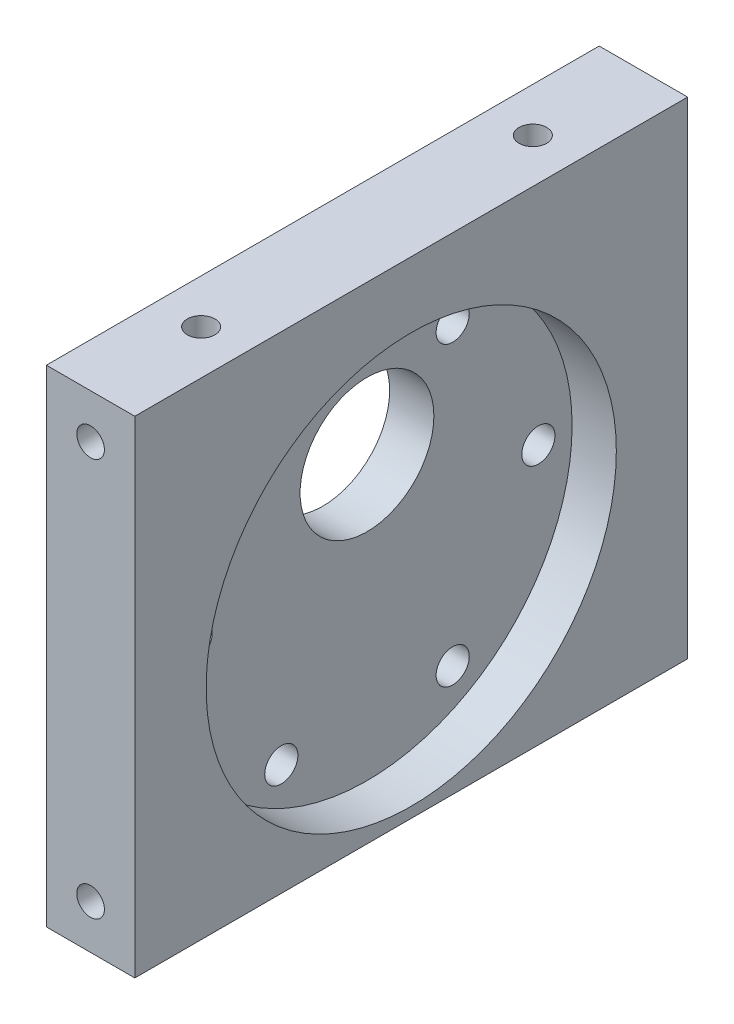
SolidWorks part; units mm, degrees
material "POM Acetal Copolymer"
ref_plane "Front Plane" through (0, 0, 0) normal (0, 0, 1) x (1, 0, 0)
ref_plane "Top Plane" through (0, 0, 0) normal (0, 1, 0) x (1, 0, 0)
ref_plane "Right Plane" through (0, 0, 0) normal (1, 0, 0) x (0, 0, -1)
sketch "Sketch1" plane through (0, 0, 0) normal (0, 1, 0) x (1, 0, 0)
  line L1 (0, 0) -> (8, 0)
  line L2 (0, 0) -> (0, 50)
  line L3 (0, 50) -> (8, 50)
  line L4 (8, 0) -> (8, 50)
  dimension "D1" = 50
  dimension "D2" = 8
extrude "Boss-Extrude1" add sketch "Sketch1" along normal blind 44
hole_wizard "Tap Drill for M3 Tap1" positions "Sketch3" profile "Sketch2" hole size "M3" standard "ISO"
sketch "Sketch3" plane through (0, 44, 0) normal (0, 1, 0) x (-1, 0, 0)
  line L0 (0, 0) -> (-8, 0) construction
  line L1 (-8, 0) -> (-8, -50) construction
  line L2 (-8, -50) -> (0, -50) construction
  point P0 (-4, -10)
  point P1 (-4, -40)
  point P6 (-4, -50)
  dimension "D1" = 10
  dimension "D2" = 4
  dimension "D3" = 10
sketch "Sketch2" plane through (4, 44, -10) normal (1, 0, 0) x (0, 0, 1)
  line L0 (0, 0) -> (0, 10.7511)
  line L1 (0, 10.7511) -> (1.25, 10)
  line L2 (1.25, 10) -> (1.25, 0)
  line L5 (1.25, 0) -> (0, 0)
  line L10 (0, 10.7511) -> (-1.25, 10) construction
  line L11 (0, -6.35) -> (0, 107.95) construction
  dimension "Hole Dia." = 2.5
  dimension "Hole Depth" = 10
  dimension "Drill Angle" = 118
hole_wizard "Tap Drill for M3 Tap2" positions "Sketch5" profile "Sketch4" hole size "M3" standard "ISO"
sketch "Sketch5" plane through (0, 0, 0) normal (0, -1, 0) x (1, 0, 0)
  line L0 (8, 0) -> (8, -50) construction
  line L1 (0, 0) -> (8, 0) construction
  line L2 (8, -50) -> (0, -50) construction
  point P0 (4, -10)
  point P1 (4, -40)
  dimension "D1" = 4
  dimension "D2" = 10
  dimension "D3" = 10
sketch "Sketch4" plane through (4, 0, -10) normal (1, 0, 0) x (0, 0, -1)
  line L0 (0, 0) -> (0, 7.7511)
  line L1 (0, 7.7511) -> (1.25, 7)
  line L2 (1.25, 7) -> (1.25, 0)
  line L5 (1.25, 0) -> (0, 0)
  line L10 (0, 7.7511) -> (-1.25, 7) construction
  line L11 (0, -6.35) -> (0, 107.95) construction
  dimension "Hole Dia." = 2.5
  dimension "Hole Depth" = 7
  dimension "Drill Angle" = 118
sketch "Sketch6" plane through (8, 0, 0) normal (1, 0, 0) x (0, 0, -1)
  line L0 (0, 44) -> (0, 0) construction
  line L1 (0, 0) -> (50, 0) construction
  circle A0 centre (25, 19.5) radius 18.55
  dimension "D2" = 37.1
  dimension "D1" = 25
  dimension "D3" = 19.5
extrude "Cut-Extrude1" cut sketch "Sketch6" against normal blind 4
sketch "Sketch7" plane through (4, 0, 0) normal (1, 0, 0) x (0, 0, -1)
  line L0 (0, 0) -> (50, 0) construction
  line L1 (6.45, 19.5) -> (25, 19.5) construction
  circle A0 centre (25, 26.5) radius 6.05
  circle A1 centre (25, 19.5) radius 18.55 construction
  circle A3 centre (9.5, 19.5) radius 1.5
  circle A4 centre (25, 19.5) radius 18.55 construction
  dimension "D1" = 12.1
  dimension "D4" = 3
  dimension "D2" = 25
  dimension "D3" = 7
  dimension "D5" = 15.5
extrude "Cut-Extrude2" cut sketch "Sketch7" against normal up to next
pattern_circular "CirPattern1" count 6 over 360 about axis through (8, 19.5, -25) along (1, 0, 0) of face at (4, 19.5, -11)
chamfer "Chamfer1" distance 1.4 angle 45 6 edges at (0, 19.5, -39) (0, 7.3756, -32) (0, 7.3756, -18) (0, 19.5, -11) (0, 31.6244, -18) (0, 31.6244, -32)
sketch "Sketch8" plane through (0, 0, 0) normal (0, 0, 1) x (1, 0, 0)
  line L0 (0, 44) -> (0, 0) construction
  line L1 (0, 44) -> (8, 44) construction
  circle A0 centre (4, 40) radius 1.25
  circle A1 centre (4, 4) radius 1.25
  dimension "D1" = 2.5
  dimension "D2" = 4
  dimension "D3" = 4
  dimension "D4" = 36
extrude "Cut-Extrude3" cut sketch "Sketch8" against normal blind 8
sketch "Sketch9" plane through (0, 0, -50) normal (0, 0, -1) x (-1, 0, 0)
  line L0 (-8, 44) -> (-8, 0) construction
  line L1 (-8, 44) -> (0, 44) construction
  circle A0 centre (-4, 40) radius 1.25
  circle A1 centre (-4, 4) radius 1.25
  dimension "D1" = 2.5
  dimension "D2" = 4
  dimension "D3" = 36
  dimension "D4" = 4
extrude "Cut-Extrude4" cut sketch "Sketch9" against normal blind 8
